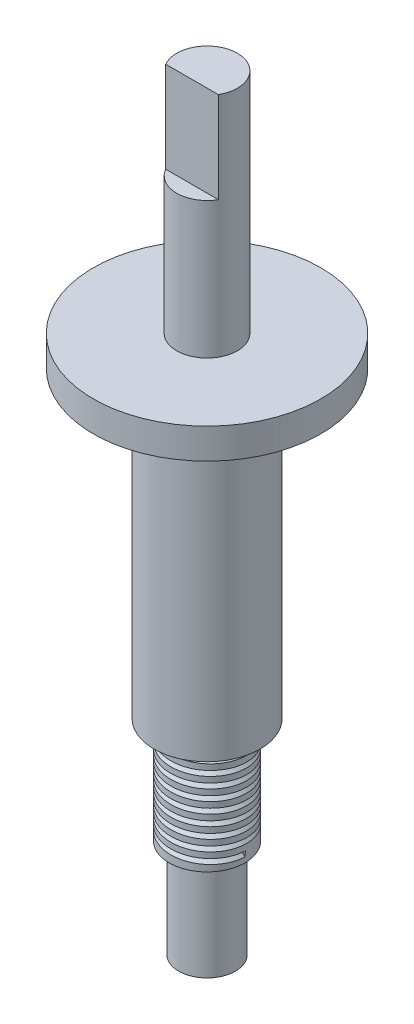
SolidWorks part; units mm, degrees
ref_plane "Front Plane" through (0, 0, 0) normal (0, 0, 1) x (1, 0, 0)
ref_plane "Top Plane" through (0, 0, 0) normal (0, 1, 0) x (1, 0, 0)
ref_plane "Right Plane" through (0, 0, 0) normal (1, 0, 0) x (0, 0, -1)
sketch "Sketch1" plane through (0, 0, 0) normal (0, 1, 0) x (1, 0, 0)
  circle A0 centre (0, 0) radius 15
  dimension "D1" = 30
extrude "Boss-Extrude1" add sketch "Sketch1" along normal blind 101
sketch "Sketch2" plane through (0, 101, 0) normal (0, 1, 0) x (1, 0, 0)
  circle A0 centre (0, 0) radius 4
  dimension "D1" = 8
extrude "Cut-Extrude1" cut sketch "Sketch2" against normal blind 30 flip side to cut
sketch "Sketch3" plane through (0, 0, 0) normal (0, -1, 0) x (1, 0, 0)
  circle A0 centre (0, 0) radius 7
  dimension "D1" = 14
extrude "Cut-Extrude2" cut sketch "Sketch3" against normal blind 67 flip side to cut
sketch "Sketch4" plane through (0, 0, 0) normal (0, -1, 0) x (1, 0, 0)
  circle A0 centre (0, 0) radius 5
  dimension "D1" = 10
extrude "Cut-Extrude5" cut sketch "Sketch4" against normal blind 27 flip side to cut
sketch "Sketch6" plane through (0, 0, 0) normal (0, -1, 0) x (1, 0, 0)
  circle A0 centre (0, 0) radius 3.75
  dimension "D1" = 7.5
extrude "Cut-Extrude6" cut sketch "Sketch6" against normal blind 13 flip side to cut
sketch "Sketch8" plane through (0, 27, 0) normal (0, -1, 0) x (-1, 0, 0)
  circle A0 centre (0, 0) radius 5
curve "Helix/Spiral1" pitch 1.4375 height 13.6562 turns 9.5
ref_plane "Plane3" through (5, 13.3437, 0) normal (0, -0.0457, -0.999) x (-1, 0, 0)
sketch "Sketch9" plane through (5, 13.3437, 0) normal (0, -0.0457, -0.999) x (-1, 0, 0)
  line L1 (0.5189, 0.8878) -> (-2.1577, 1.5046)
  line L2 (-2.1577, 1.5046) -> (-1.3536, -1.1218)
  line L3 (-1.3536, -1.1218) -> (0.5189, 0.8878)
  circle A0 centre (-0.9975, 0.4235) radius 1.5858 construction
sweep "Cut-Sweep1" cut profiles "Sketch9" path "Helix/Spiral1"
sketch "Sketch10" plane through (0, 101, 0) normal (0, 1, 0) x (1, 0, 0)
  line L0 (0, 0) -> (0, -1.983) construction
  line L1 (-3.4739, -1.983) -> (3.4739, -1.983)
  circle A0 centre (0, 0) radius 4 construction
  circle A2 centre (0, 0) radius 4
  arc A3 (-3.4739, -1.983) -> (3.4739, -1.983) centre (0, 0) cw
  arc A4 (-3.4739, -1.983) -> (3.4739, -1.983) centre (0, 0) ccw
  circle M1 centre (0, 0) radius 4
extrude "Cut-Extrude7" cut sketch "Sketch10" against normal blind 12 contours L1 M1
sketch "Sketch11" plane through (0, 71, 0) normal (0, 1, 0) x (1, 0, 0)
  line L0 (15, 0) -> (-15, 0) construction
  circle A0 centre (0, 0) radius 15 construction
ref_plane "Plane4" through (0, 0, 0) normal (0, 0, 1) x (1, 0, 0)
ref_plane "Plane5" through (0, 0, -5) normal (0, 0, 1) x (1, 0, 0)
sketch "Sketch12" plane through (0, 0, -5) normal (0, 0, 1) x (1, 0, 0)
  line L2 (-2.183, 29.0564) -> (-2.183, 63.0564)
  line L4 (1.317, 29.0564) -> (1.317, 63.0564)
  arc A0 (1.317, 63.0564) -> (-2.183, 63.0564) centre (-0.433, 63.0564) ccw
  arc A1 (-2.183, 29.0564) -> (1.317, 29.0564) centre (-0.433, 29.0564) ccw
  dimension "D1" = 34
  dimension "D2" = 3.5
extrude "Cut-Extrude8" cut sketch "Sketch12" against normal blind 10
